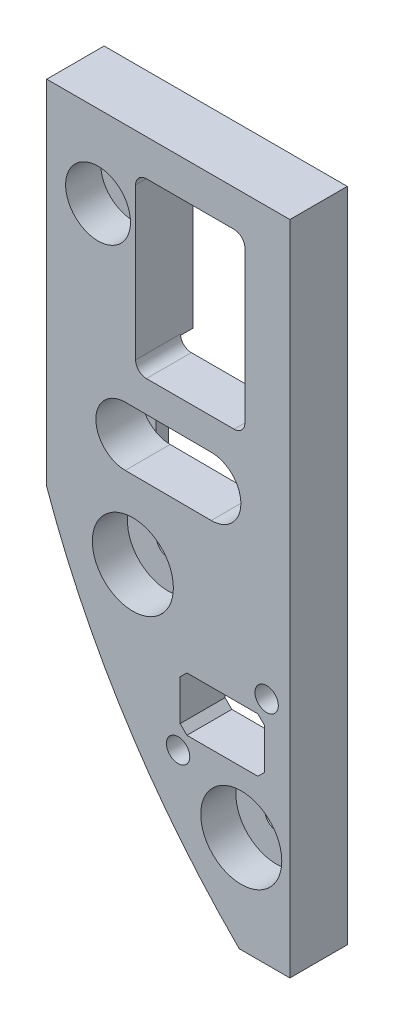
SolidWorks part; units mm, degrees
material "PET"
ref_plane "Front" through (0, 0, 0) normal (0, 0, 1) x (1, 0, 0)
ref_plane "Top" through (0, 0, 0) normal (0, 1, 0) x (1, 0, 0)
ref_plane "Right" through (0, 0, 0) normal (1, 0, 0) x (0, 0, -1)
sketch "Sketch1" plane through (0, 0, 0) normal (0, 0, 1) x (1, 0, 0)
  line L0 (-1.8976, -121.9236) -> (-1.8976, -95.5711)
  line L1 (-1.8976, -95.5711) -> (-12.1665, -95.5711)
  line L2 (-12.1665, -95.5711) -> (-16.929, -90.8086)
  line L3 (-16.929, -90.8086) -> (-23.4876, -90.8086)
  line L4 (0, -17.78) -> (-45.72, -17.78)
  line L5 (-45.72, -17.78) -> (-45.72, -84.1375)
  line L6 (-9.525, -141.2875) -> (0, -141.2875)
  line L7 (0, -141.2875) -> (0, -17.78)
  line L8 (0, -17.78) -> (-45.72, -17.78)
  line L9 (-45.72, -17.78) -> (-45.72, -84.1375)
  line L10 (-9.525, -141.2875) -> (0, -141.2875)
  line L11 (0, -141.2875) -> (0, -17.78)
  line L12 (-23.4876, -90.8086) -> (-23.4876, -117.1611)
  line L13 (-23.4876, -117.1611) -> (-13.2186, -117.1611)
  line L14 (-13.2186, -117.1611) -> (-9.5028, -120.877)
  line L15 (-7.2795, -121.9236) -> (-1.8976, -121.9236)
  line L16 (-32.385, -80.4545) -> (-9.525, -80.4545)
  line L17 (-9.525, -80.4545) -> (-9.525, -76.6445)
  line L18 (-9.525, -76.6445) -> (-13.335, -72.8345)
  line L19 (-13.335, -72.8345) -> (-13.335, -56.642)
  line L20 (-13.335, -56.642) -> (-36.195, -56.642)
  line L21 (-36.195, -56.642) -> (-36.195, -60.452)
  line L22 (-36.195, -60.452) -> (-32.385, -64.262)
  line L23 (-32.385, -64.262) -> (-32.385, -80.4545)
  line L24 (-32.385, -80.4545) -> (-9.525, -80.4545) construction
  line L25 (-9.525, -80.4545) -> (-9.525, -76.6445) construction
  line L26 (-9.525, -76.6445) -> (-13.335, -72.8345) construction
  line L27 (-13.335, -72.8345) -> (-13.335, -56.642) construction
  line L28 (-13.335, -56.642) -> (-36.195, -56.642) construction
  line L29 (-36.195, -56.642) -> (-36.195, -60.452) construction
  line L30 (-36.195, -60.452) -> (-32.385, -64.262) construction
  line L31 (-32.385, -64.262) -> (-32.385, -80.4545) construction
  line L32 (-3.1676, -120.6536) -> (-3.1676, -96.8411)
  line L33 (-3.1676, -96.8411) -> (-12.6926, -96.8411)
  line L34 (-12.6926, -96.8411) -> (-17.4551, -92.0786)
  line L35 (-17.4551, -92.0786) -> (-22.2176, -92.0786)
  line L36 (-22.2176, -92.0786) -> (-22.2176, -115.8911)
  line L37 (-22.2176, -115.8911) -> (-12.6926, -115.8911)
  line L38 (-12.6926, -115.8911) -> (-7.9301, -120.6536)
  line L39 (-7.9301, -120.6536) -> (-3.1676, -120.6536)
  line L40 (-3.1676, -120.6536) -> (-3.1676, -96.8411) construction
  line L41 (-3.1676, -96.8411) -> (-12.6926, -96.8411) construction
  line L42 (-12.6926, -96.8411) -> (-17.4551, -92.0786) construction
  line L43 (-17.4551, -92.0786) -> (-22.2176, -92.0786) construction
  line L44 (-22.2176, -92.0786) -> (-22.2176, -115.8911) construction
  line L45 (-22.2176, -115.8911) -> (-12.6926, -115.8911) construction
  line L46 (-12.6926, -115.8911) -> (-7.9301, -120.6536) construction
  line L47 (-7.9301, -120.6536) -> (-3.1676, -120.6536) construction
  line L48 (-33.655, -81.7245) -> (-8.255, -81.7245)
  line L49 (-8.255, -81.7245) -> (-8.255, -76.1184)
  line L50 (-8.255, -76.1184) -> (-12.065, -72.3084)
  line L51 (-12.065, -72.3084) -> (-12.065, -57.1627)
  line L52 (-29.0068, -55.372) -> (-37.465, -55.372)
  line L53 (-37.465, -55.372) -> (-37.465, -60.9781)
  line L54 (-37.465, -60.9781) -> (-33.655, -64.7881)
  line L55 (-33.655, -64.7881) -> (-33.655, -81.7245)
  line L80 (-8.4582, -55.1307) -> (-8.4582, -26.6573)
  line L81 (-26.9748, -57.1627) -> (-10.4902, -57.1627)
  line L82 (-29.0068, -26.6573) -> (-29.0068, -55.1307)
  line L83 (-10.4902, -24.6253) -> (-26.9748, -24.6253)
  line L84 (-8.4582, -55.1307) -> (-8.4582, -26.6573)
  line L86 (-29.0068, -26.6573) -> (-29.0068, -55.372)
  line L87 (-10.4902, -24.6253) -> (-26.9748, -24.6253)
  line L2565 (-12.065, -72.3084) -> (-12.065, -55.372) construction
  line L2566 (-12.065, -55.372) -> (-37.465, -55.372) construction
  line L2567 (-12.065, -57.1627) -> (-10.4902, -57.1627)
  line L2568 (-13.2186, -117.1611) -> (-8.4561, -121.9236) construction
  line L2569 (-8.4561, -121.9236) -> (-1.8976, -121.9236) construction
  circle A1 centre (-36.1315, -33.274) radius 2.1526
  circle A2 centre (-36.1315, -33.274) radius 2.1526
  circle A3 centre (-29.5275, -88.7095) radius 2.1526
  circle A4 centre (-29.5275, -88.7095) radius 2.1527
  circle A5 centre (-9.144, -122.9995) radius 2.1526
  arc A6 (-9.5028, -120.877) -> (-7.2795, -121.9236) centre (-9.144, -122.9995) ccw
  arc A7 (-45.72, -84.1375) -> (-9.525, -141.2875) centre (97.9169, -33.2042) ccw
  arc A8 (-45.72, -84.1375) -> (-9.525, -141.2875) centre (97.9169, -33.2042) ccw
  arc A16 (-8.4582, -26.6573) -> (-10.4902, -24.6253) centre (-10.4902, -26.6573) ccw
  arc A17 (-10.4902, -57.1627) -> (-8.4582, -55.1307) centre (-10.4902, -55.1307) ccw
  arc A18 (-29.0068, -55.1307) -> (-26.9748, -57.1627) centre (-26.9748, -55.1307) ccw
  arc A19 (-26.9748, -24.6253) -> (-29.0068, -26.6573) centre (-26.9748, -26.6573) ccw
  arc A20 (-8.4582, -26.6573) -> (-10.4902, -24.6253) centre (-10.4902, -26.6573) ccw
  arc A21 (-10.4902, -57.1627) -> (-8.4582, -55.1307) centre (-10.4902, -55.1307) ccw
  arc A23 (-26.9748, -24.6253) -> (-29.0068, -26.6573) centre (-26.9748, -26.6573) ccw
  dimension "D1" = 0
  dimension "D2" = 0
  dimension "D3" = 0
  dimension "D4" = 0
  dimension "D5" = 0
  dimension "D6" = 0
  dimension "D7" = 1.27
  dimension "D8" = 1.27
  dimension "D9" = 1.27
extrude "Boss-Extrude1" add sketch "Sketch1" along normal offset from surface (2.3495 mm away) 0.762 offset beyond the face yes
sketch "Sketch2" plane through (0, 0, 2.3495) normal (0, 0, 1) x (1, 0, 0)
  line L0 (-12.6926, -105.7961) -> (-12.6926, -106.9361) construction
  line L4 (-9.525, -141.2875) -> (0, -141.2875)
  line L5 (0, -141.2875) -> (0, -17.78)
  line L6 (0, -17.78) -> (-45.72, -17.78)
  line L7 (-45.72, -17.78) -> (-45.72, -84.1375)
  line L8 (-9.525, -141.2875) -> (0, -141.2875)
  line L9 (0, -141.2875) -> (0, -17.78)
  line L10 (0, -17.78) -> (-45.72, -17.78)
  line L11 (-45.72, -17.78) -> (-45.72, -84.1375)
  line L13 (-4.7551, -111.4461) -> (-20.6301, -111.4461)
  line L14 (-4.7551, -111.4461) -> (-4.7551, -101.2861)
  line L15 (-4.7551, -101.2861) -> (-20.6301, -101.2861)
  line L16 (-20.6301, -111.4461) -> (-20.6301, -101.2861)
  line L17 (-4.7551, -111.4461) -> (-20.6301, -101.2861) construction
  line L18 (-4.7551, -101.2861) -> (-20.6301, -111.4461) construction
  line L19 (-22.8475, -67.6357) -> (-22.8475, -69.5407) construction
  line L20 (-22.53, -67.6357) -> (-23.165, -67.6357) construction
  line L21 (-23.165, -69.5407) -> (-22.53, -69.5407) construction
  line L22 (-14.7705, -68.6282) -> (-30.9245, -68.5483) construction
  line L23 (-14.798, -74.1844) -> (-30.952, -74.1044)
  line L24 (-14.743, -63.0721) -> (-30.897, -62.9921)
  line L33 (-8.4582, -55.1307) -> (-8.4582, -26.6573)
  line L34 (-26.9748, -57.1627) -> (-10.4902, -57.1627)
  line L35 (-29.0068, -26.6573) -> (-29.0068, -55.1307)
  line L36 (-10.4902, -24.6253) -> (-26.9748, -24.6253)
  line L37 (-8.4582, -55.1307) -> (-8.4582, -26.6573)
  line L38 (-26.9748, -57.1627) -> (-10.4902, -57.1627)
  line L39 (-29.0068, -26.6573) -> (-29.0068, -55.1307)
  line L40 (-10.4902, -24.6253) -> (-26.9748, -24.6253)
  circle A0 centre (-9.144, -122.9995) radius 2.1526 construction
  arc A1 (-45.72, -84.1375) -> (-9.525, -141.2875) centre (97.9169, -33.2042) ccw
  arc A2 (-45.72, -84.1375) -> (-9.525, -141.2875) centre (97.9169, -33.2042) ccw
  circle A3 centre (-9.144, -122.9995) radius 2.1526
  circle A4 centre (-29.5275, -88.7095) radius 2.1526 construction
  circle A5 centre (-29.5275, -88.7095) radius 2.1527
  circle A10 centre (-21.016, -114.6896) radius 1.4336 construction
  circle A11 centre (-21.016, -114.6896) radius 1.4336 construction
  circle A12 centre (-4.3691, -98.0426) radius 1.4336 construction
  circle A13 centre (-4.3691, -98.0426) radius 1.4336 construction
  circle A15 centre (-30.9245, -68.5483) radius 1.4336 construction
  circle A17 centre (-30.9245, -68.5483) radius 1.4336 construction
  circle A18 centre (-21.016, -114.6896) radius 2.1956
  circle A19 centre (-4.3691, -98.0426) radius 2.1956
  circle A20 centre (-30.9245, -68.5483) radius 2.1956 construction
  arc A22 (-14.798, -74.1844) -> (-14.743, -63.0721) centre (-14.7705, -68.6282) ccw
  arc A23 (-30.897, -62.9921) -> (-30.952, -74.1044) centre (-30.9245, -68.5483) ccw
  arc A32 (-8.4582, -26.6573) -> (-10.4902, -24.6253) centre (-10.4902, -26.6573) ccw
  arc A33 (-10.4902, -57.1627) -> (-8.4582, -55.1307) centre (-10.4902, -55.1307) ccw
  arc A34 (-29.0068, -55.1307) -> (-26.9748, -57.1627) centre (-26.9748, -55.1307) ccw
  arc A35 (-26.9748, -24.6253) -> (-29.0068, -26.6573) centre (-26.9748, -26.6573) ccw
  arc A36 (-8.4582, -26.6573) -> (-10.4902, -24.6253) centre (-10.4902, -26.6573) ccw
  arc A37 (-10.4902, -57.1627) -> (-8.4582, -55.1307) centre (-10.4902, -55.1307) ccw
  arc A38 (-29.0068, -55.1307) -> (-26.9748, -57.1627) centre (-26.9748, -55.1307) ccw
  arc A39 (-26.9748, -24.6253) -> (-29.0068, -26.6573) centre (-26.9748, -26.6573) ccw
  circle A472 centre (-36.1315, -33.274) radius 2.1526 construction
  circle A473 centre (-36.1315, -33.274) radius 2.1526
  point P19 (-22.8475, -68.5882)
  point P32 (-12.6926, -106.3661)
  dimension "D3" = 15.875
  dimension "D4" = 10.16
  dimension "D5" = 11.1125
  dimension "D6" = 1.27
  dimension "D1" = 0
  dimension "D2" = 0.762
extrude "Boss-Extrude2" add sketch "Sketch2" along normal up to surface (8.4455 mm away)
sketch "Sketch3" plane through (0, 0, 2.3495) normal (0, 0, -1) x (-1, 0, 0)
  circle A0 centre (34.29, -58.547) radius 1.3525 construction
  circle A1 centre (11.43, -78.5495) radius 1.3525 construction
  circle A2 centre (5.5488, -118.2724) radius 1.3525 construction
  circle A3 centre (19.8363, -94.4599) radius 1.3525 construction
  circle A4 centre (34.29, -58.547) radius 1.3525 construction
  circle A5 centre (11.43, -78.5495) radius 1.3525 construction
  circle A6 centre (5.5488, -118.2724) radius 1.3525 construction
  circle A7 centre (19.8363, -94.4599) radius 1.3525 construction
  circle A8 centre (34.29, -58.547) radius 1.2255
  circle A9 centre (11.43, -78.5495) radius 1.2255
  circle A10 centre (5.5488, -118.2724) radius 1.2255
  circle A11 centre (19.8363, -94.4599) radius 1.2255
  dimension "D1" = 0.127
extrude "Boss-Extrude3" add sketch "Sketch3" along normal blind 2.159
chamfer "Chamfer1" distance 0.254 angle 45 4 edges at (-35.5155, -58.547, 0.1905) (-12.6555, -78.5495, 0.1905) (-21.0619, -94.4599, 0.1905) (-6.7744, -118.2724, 0.1905)
chamfer "Chamfer2" distance 1.27 angle 45 4 edges at (-20.6301, -101.2861, 6.5723) (-20.6301, -111.4461, 6.5723) (-4.7551, -111.4461, 6.5723) (-4.7551, -101.2861, 6.5723)
sketch "Sketch5" plane through (0, 0, 10.795) normal (0, 0, 1) x (1, 0, 0)
  circle A0 centre (-9.144, -122.9995) radius 6.35 construction
  circle A1 centre (-29.5275, -88.7095) radius 6.35 construction
  circle A2 centre (-36.068, -33.2105) radius 4.826 construction
  circle A6 centre (-9.144, -122.9995) radius 6.35 construction
  circle A7 centre (-29.5275, -88.7095) radius 6.35 construction
  circle A8 centre (-36.068, -33.2105) radius 4.826 construction
  circle A9 centre (-9.144, -122.9995) radius 7.62
  circle A10 centre (-29.5275, -88.7095) radius 7.62
  circle A11 centre (-36.068, -33.2105) radius 6.096
  dimension "D1" = 1.27
extrude "Cut-Extrude1" cut sketch "Sketch5" against normal blind 6.604
